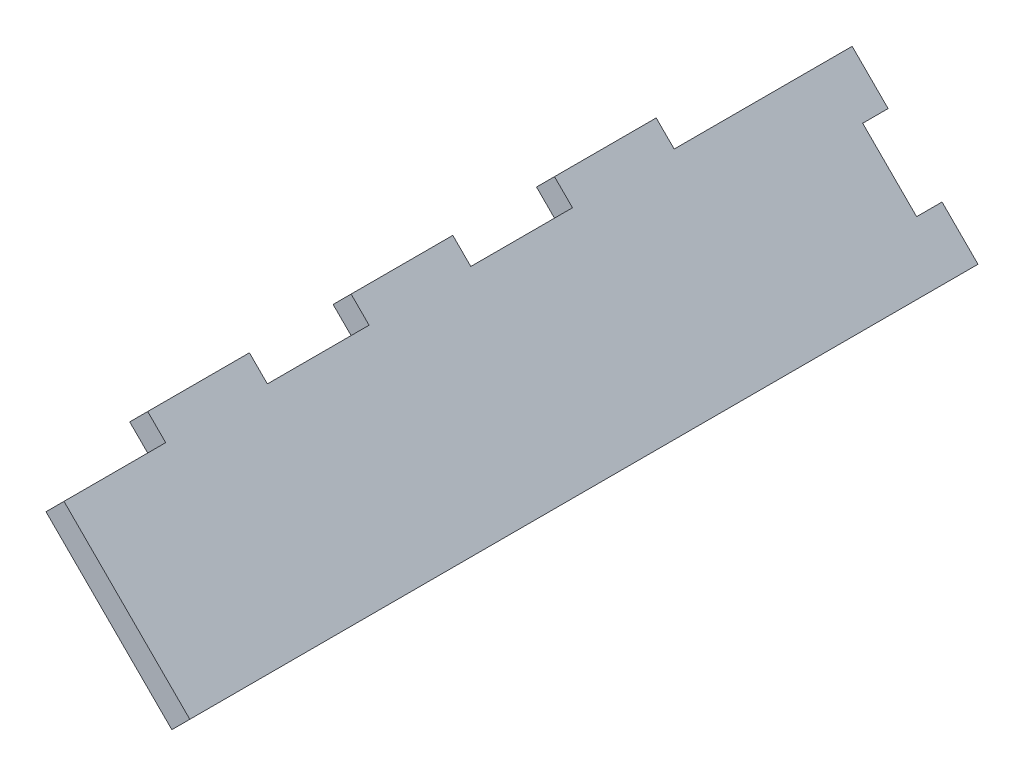
SolidWorks part; units mm, degrees
ref_plane "Front Plane" through (0, 0, 0) normal (0, 0, 1) x (1, 0, 0)
ref_plane "Top Plane" through (0, 0, 0) normal (0, 1, 0) x (1, 0, 0)
ref_plane "Right Plane" through (0, 0, 0) normal (1, 0, 0) x (0, 0, -1)
sketch "Sketch1" plane through (0, 0, 0) normal (0, 0, 1) x (1, 0, 0)
  line L0 (-105.5101, 43.1479) -> (-54.0999, -8.2622) construction
  line L1 (-21.895, -44.9573) -> (-64.9957, -1.8565) construction
  line L2 (-60.5056, 2.6336) -> (-17.4048, -40.4672) construction
  line L3 (-71.393, 41.3598) -> (-39.9621, 9.9289)
  line L4 (-71.393, 41.3598) -> (-66.9029, 45.85)
  line L5 (-39.9621, 9.9289) -> (-35.472, 14.4191)
  line L6 (-66.9029, 45.85) -> (-35.472, 14.4191)
  line L7 (-72.2911, -22.4) -> (-103.722, 9.0309) construction
  line L8 (-76.7812, -26.8901) -> (-72.2911, -22.4) construction
extrude "Boss-Extrude1" add sketch "Sketch1" along normal up to surface (190.5 mm away)
sketch "Sketch2" plane through (-56.3764, 56.3764, 0) normal (-0.7071, 0.7071, 0) x (0, 0, 1)
  line L0 (190.5, -14.8867) -> (0, -14.8867) construction
  line L1 (165.1, -14.8867) -> (139.7, -14.8867)
  line L2 (165.1, -14.8867) -> (165.1, -21.2367)
  line L3 (165.1, -21.2367) -> (139.7, -21.2367)
  line L4 (139.7, -14.8867) -> (139.7, -21.2367)
  line L5 (190.5, -21.2367) -> (0, -21.2367) construction
  dimension "D1" = 25.4
  dimension "D2" = 25.4
extrude "Boss-Extrude2" add sketch "Sketch2" along normal blind 6.35
pattern_linear "LPattern1" count 3 spacing 50.8 along (0, 0, -1) of "Boss-Extrude2"
sketch "Sketch3" plane through (0, 0, 0) normal (0, 0, -1) x (-1, 0, 0)
  line L0 (71.393, 41.3598) -> (62.4128, 32.3796)
  line L1 (71.393, 41.3598) -> (39.9621, 9.9289) construction
  line L2 (62.4128, 32.3796) -> (57.9227, 36.8697)
  line L3 (35.472, 14.4191) -> (66.9029, 45.85) construction
  line L4 (57.9227, 36.8697) -> (66.9029, 45.85)
  line L5 (66.9029, 45.85) -> (71.393, 41.3598)
  dimension "D1" = 12.7
extrude "Boss-Extrude3" add sketch "Sketch3" along normal blind 6.35
pattern_linear "LPattern2" count 2 spacing 31.75 along (0.7071, -0.7071, 0) of "Boss-Extrude3"
